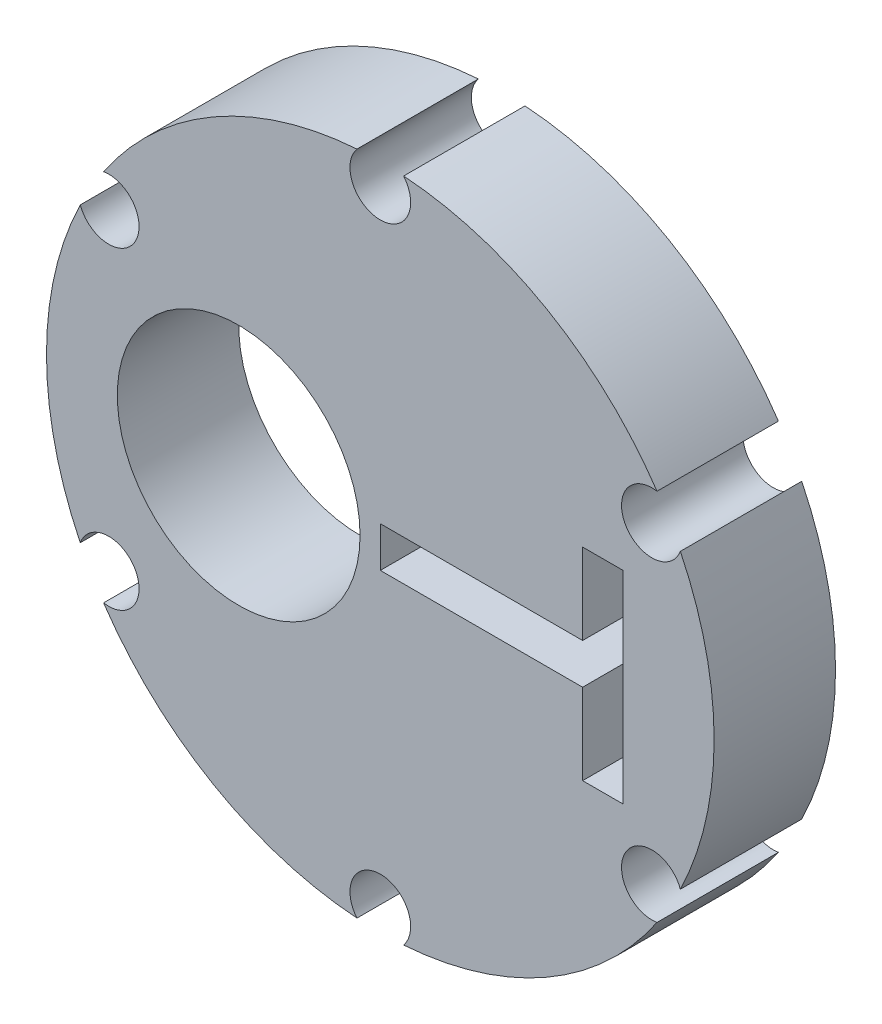
SolidWorks part; units mm, degrees
material "ABS"
ref_plane "Front Plane" through (0, 0, 0) normal (0, 0, 1) x (1, 0, 0)
ref_plane "Top Plane" through (0, 0, 0) normal (0, 1, 0) x (1, 0, 0)
ref_plane "Right Plane" through (0, 0, 0) normal (1, 0, 0) x (0, 0, -1)
sketch "Sketch1" plane through (0, 0, 0) normal (0, 0, 1) x (1, 0, 0)
  circle A0 centre (0, 0) radius 16.5
  dimension "D1" = 33
extrude "Boss-Extrude1" add sketch "Sketch1" along normal blind 6
sketch "Sketch2" plane through (0, 0, 6) normal (0, 0, 1) x (1, 0, 0)
  circle A0 centre (0, 15.5) radius 1.5
  circle A1 centre (13.4234, 7.75) radius 1.5
  circle A2 centre (13.4234, -7.75) radius 1.5
  circle A3 centre (0, -15.5) radius 1.5
  circle A4 centre (-13.4234, -7.75) radius 1.5
  circle A5 centre (-13.4234, 7.75) radius 1.5
  point P15 (0, 0)
  dimension "D1" = 3
  dimension "D2" = 15.5
  dimension "D3" = 6
extrude "Cut-Extrude1" cut sketch "Sketch2" against normal through all
sketch "Sketch3" plane through (0, 0, 6) normal (0, 0, 1) x (1, 0, 0)
  line L0 (-7, 0) -> (0, 0) construction
  circle A0 centre (-7, 0) radius 6
  dimension "D1" = 12
  dimension "D3" = 7
extrude "Cut-Extrude2" cut sketch "Sketch3" against normal through all
sketch "Sketch5" plane through (0, 0, 6) normal (0, 0, 1) x (1, 0, 0)
  line L1 (12, 5) -> (10, 5)
  line L2 (12, 5) -> (12, -5)
  line L3 (12, -5) -> (10, -5)
  line L4 (10, 5) -> (10, 1)
  line L5 (10, -1) -> (10, -5)
  line L6 (0, 1) -> (10, 1)
  line L7 (0, 1) -> (0, -1)
  line L8 (0, -1) -> (10, -1)
  point P10 (0, 0)
  dimension "D1" = 10
  dimension "D2" = 2
extrude "Cut-Extrude3" cut sketch "Sketch5" against normal through all
equation "\"smallPulleyTeeth\"= 15"
equation "\"largePulleyTeeth\"= 30"
equation "\"eighthThick\"= 2.9mm"
equation "\"sixteenthThick\" = 1.7mm"
equation "\"wheelEighthThick\"=3.0mm"
equation "\"quarterThick\"=6.0mm"
equation "\"OD\" = 145mm"
equation "\"puckAngle\" = 60.5deg"
equation "\"puckDiam\" = 76.5mm"
equation "\"axlePress\" = 5.9mm"
equation "\"D1@Boss-Extrude1\"=\"quarterThick\""
